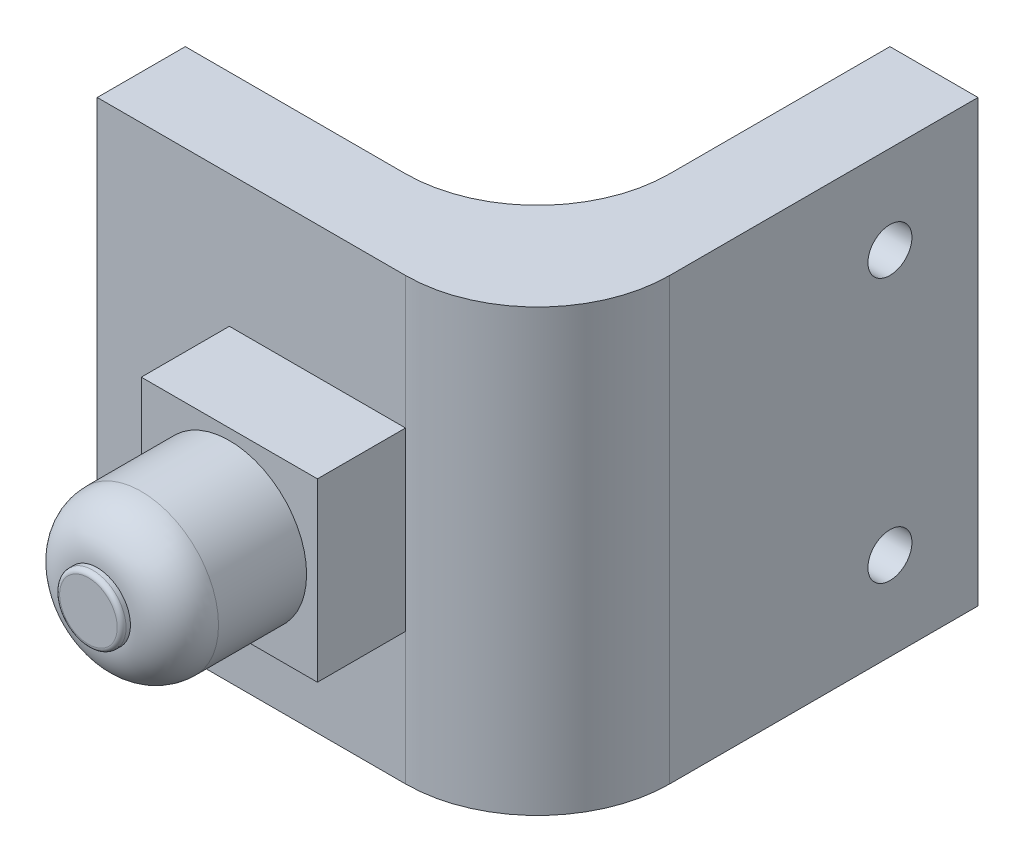
SolidWorks part; units mm, degrees
other "Camera1"
ref_plane "Front Plane" through (0, 0, 0) normal (0, 0, 1) x (1, 0, 0)
ref_plane "Top Plane" through (0, 0, 0) normal (0, 1, 0) x (1, 0, 0)
ref_plane "Right Plane" through (0, 0, 0) normal (1, 0, 0) x (0, 0, -1)
sketch "Sketch1" plane through (0, 0, 0) normal (0, 1, 0) x (1, 0, 0)
  line L0 (0, 0) -> (50, 0)
  line L1 (50, 0) -> (50, 50)
  line L2 (50, 50) -> (40, 50)
  line L3 (40, 50) -> (40, 10)
  line L4 (40, 10) -> (0, 10)
  line L5 (0, 10) -> (0, 0)
  dimension "D1" = 50
  dimension "D2" = 50
  dimension "D3" = 10
  dimension "D4" = 10
extrude "Boss-Extrude1" add sketch "Sketch1" along normal blind 50
sketch "Sketch2" plane through (40, 0, 0) normal (-1, 0, 0) x (0, 0, 1)
  line L0 (-50, 50) -> (-10, 50) construction
  line L2 (-50, 50) -> (-50, 0) construction
  line L4 (-50, 0) -> (-10, 0) construction
  circle A0 centre (-40, 10) radius 2.5
  circle A1 centre (-40, 40) radius 2.5
  point P2 (0, 0)
  point P9 (-50, 38.241)
  point P10 (0, 0)
  point P12 (-38.7574, 0)
  point P13 (-44.1205, -1.3991)
  dimension "D1" = 10
  dimension "D2" = 10
  dimension "D3" = 10
  dimension "D4" = 10
extrude "Cut-Extrude2" cut sketch "Sketch2" against normal blind 50 contours A0 | A1 region at (40, 10, -40)
sketch "Sketch3" plane through (0, 0, 0) normal (0, 0, 1) x (1, 0, 0)
  line L0 (0, 50) -> (0, 0) construction
  line L1 (15, 35) -> (35, 35)
  line L2 (15, 35) -> (15, 15)
  line L3 (15, 15) -> (35, 15)
  line L4 (35, 35) -> (35, 15)
  line L5 (15, 35) -> (35, 15) construction
  line L6 (15, 15) -> (35, 35) construction
  line L7 (50, 50) -> (50, 0) construction
  line L8 (0, 50) -> (50, 50) construction
  line L9 (0, 0) -> (50, 0) construction
  point P0 (25, 25)
  point P5 (28.1356, 22.4625)
  point P6 (18.572, 11.0175)
  point P7 (23.0402, 19.0133)
  point P8 (18.0233, 16.8184)
  point P9 (40.8027, 11.5004)
  dimension "D1" = 15
  dimension "D2" = 15
  dimension "D3" = 15
  dimension "D4" = 15
extrude "Boss-Extrude2" add sketch "Sketch3" along normal blind 10 contours L2 L1 L4 L3
sketch "Sketch4" plane through (0, 0, 10) normal (0, 0, 1) x (1, 0, 0)
  line L1 (15, 15) -> (35, 15) construction
  line L2 (35, 35) -> (35, 15) construction
  circle A0 centre (25, 25) radius 8.7691
  dimension "D1" = 10
  dimension "D2" = 10
extrude "Boss-Extrude3" add sketch "Sketch4" along normal blind 15 contours A0
fillet "Fillet1" radius 5 1 edges at (33.7691, 25, 25) type face fillet first side face at (33.7691, 25, 25) second side face at (33.7691, 25, 25)
fillet "Fillet2" radius 15 1 edges at (40, 25, -10) type face fillet first side face at (40, 10, -37.5) second side face at (20, 25, -10)
fillet "Fillet3" radius 15 1 edges at (50, 25, 0) type face fillet first side face at (25, 25, 0) second side face at (50, 10, -37.5)
sketch "Sketch5" plane through (0, 0, 25) normal (0, 0, 1) x (1, 0, 0)
  circle A0 centre (25.7834, 28.6677) radius 0.0186
sketch "Sketch7" plane through (0, 0, 25) normal (0, 0, 1) x (1, 0, 0)
  circle A0 centre (25, 25) radius 3.7691
  circle A1 centre (25, 25) radius 3.7691 construction
extrude "Boss-Extrude4" add sketch "Sketch7" along normal blind 1 contours A0
fillet "Fillet5" radius 0.5 1 edges at (28.7691, 25, 26) type face fillet first side face at (28.7691, 25, 26) second side face at (28.7691, 25, 26)
equation "\"a\"=16.0391"
